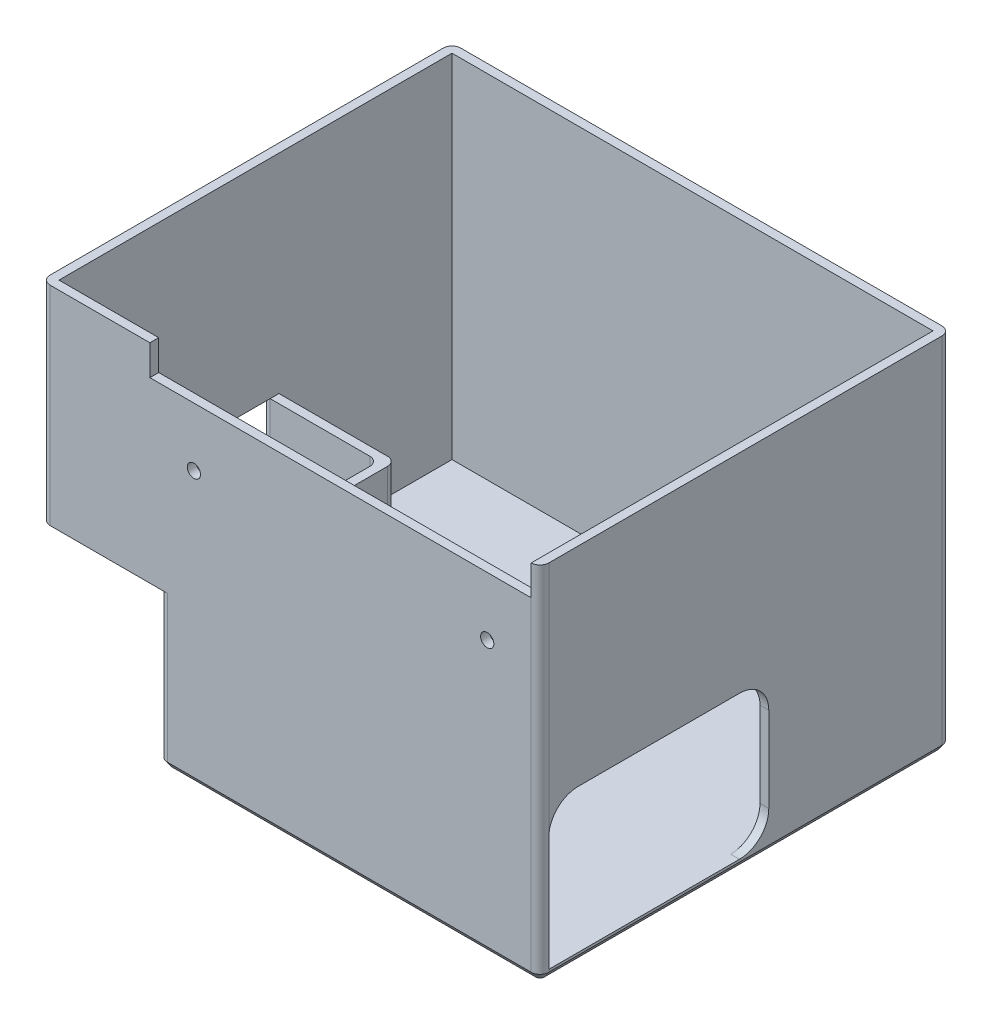
SolidWorks part; units mm, degrees
ref_plane "Front Plane" through (0, 0, 0) normal (0, 0, 1) x (1, 0, 0)
ref_plane "Top Plane" through (0, 0, 0) normal (0, 1, 0) x (1, 0, 0)
ref_plane "Right Plane" through (0, 0, 0) normal (1, 0, 0) x (0, 0, -1)
sketch "Sketch1" plane through (0, 0, 0) normal (0, 1, 0) x (1, 0, 0)
  line L1 (-85, -70) -> (85, -70)
  line L2 (-85, -70) -> (-85, 70)
  line L3 (-85, 70) -> (85, 70)
  line L4 (85, -70) -> (85, 70)
  line L5 (-85, -70) -> (85, 70) construction
  line L6 (-85, 70) -> (85, -70) construction
  point P0 (0, 0)
  dimension "D1" = 170
  dimension "D2" = 140
extrude "Boss-Extrude1" add sketch "Sketch1" along normal blind 3
sketch "Sketch3" plane through (0, 3, 0) normal (0, 1, 0) x (1, 0, 0)
  line L0 (82, -67) -> (82, 67)
  line L1 (82, 67) -> (-82, 67)
  line L2 (-82, 67) -> (-82, -67)
  line L3 (-82, -67) -> (82, -67)
  line L4 (85, -70) -> (85, 70)
  line L5 (85, 70) -> (-85, 70)
  line L6 (-85, 70) -> (-85, -70)
  line L7 (-85, -70) -> (85, -70)
  line L8 (85, -70) -> (85, 70)
  line L9 (85, 70) -> (-85, 70)
  line L10 (-85, 70) -> (-85, -70)
  line L11 (-85, -70) -> (85, -70)
  dimension "D1" = 0
  dimension "D2" = 3
extrude "Boss-Extrude2" add sketch "Sketch3" along normal blind 120
sketch "Sketch4" plane through (0, 0, 70) normal (0, 0, 1) x (1, 0, 0)
  line L0 (-85, 123) -> (85, 123) construction
  line L1 (82, 123) -> (-48, 123)
  line L2 (82, 123) -> (82, 112.7)
  line L3 (82, 112.7) -> (-48, 112.7)
  line L4 (-48, 123) -> (-48, 112.7)
  line L5 (82, 123) -> (82, 3) construction
  dimension "D1" = 10.3
  dimension "D2" = 130
extrude "Cut-Extrude1" cut sketch "Sketch4" against normal up to next
sketch "Sketch5" plane through (-85, 0, 0) normal (-1, 0, 0) x (0, 0, 1)
  line L0 (-70, 123) -> (70, 123) construction
  line L1 (-5, 0) -> (70, 0)
  line L2 (-5, 0) -> (-5, 52)
  line L3 (-5, 52) -> (70, 52)
  line L4 (70, 0) -> (70, 52)
  line L7 (-70, 0) -> (70, 0) construction
  line L8 (70, 123) -> (70, 0) construction
  dimension "D1" = 71
  dimension "D2" = 75
extrude "Cut-Extrude2" cut sketch "Sketch5" against normal blind 40
sketch "Sketch6" plane through (0, 3, 0) normal (0, 1, 0) x (1, 0, 0)
  line L0 (-45, 5) -> (-45, -67) construction
  line L1 (-82, 5) -> (-45, 5) construction
  line L2 (-45, 5) -> (-45, -67)
  line L3 (-82, 5) -> (-45, 5)
  line L4 (-82, 5) -> (-82, 8)
  line L5 (-82, 67) -> (-82, 5) construction
  line L6 (-82, 8) -> (-42, 8)
  line L7 (-42, 8) -> (-42, -67)
  line L8 (-48, -67) -> (82, -67) construction
  line L9 (-42, -67) -> (-45, -67)
  dimension "D1" = 3
extrude "Boss-Extrude3" add sketch "Sketch6" along normal up to surface (49 mm away) up to face at (-70.6667, 52, 44)
sketch "Sketch8" plane through (0, 0, 70) normal (0, 0, 1) x (1, 0, 0)
  line L0 (-48, 112.7) -> (82, 112.7) construction
  line L2 (82, 112.7) -> (82, 123) construction
  circle A0 centre (67, 92.7) radius 2.25
  circle A1 centre (-33, 92.7) radius 2.25
  dimension "D1" = 4.5
  dimension "D2" = 20
  dimension "D3" = 15
  dimension "D4" = 100
extrude "Cut-Extrude3" cut sketch "Sketch8" against normal up to next
sketch "Sketch9" plane through (85, 0, 0) normal (1, 0, 0) x (0, 0, -1)
  line L0 (-67, 3) -> (67, 3) construction
  line L2 (-67, 112.7) -> (-67, 3) construction
  line L3 (-67, 3) -> (8, 3) construction
  line L5 (-67, 112.7) -> (-67, 3) construction
  line L6 (-70, 123) -> (70, 123) construction
  line L7 (8, 3) -> (-67, 3)
  line L8 (8, 3) -> (8, 52)
  line L9 (8, 52) -> (-67, 52)
  line L10 (-67, 3) -> (-67, 52)
  point P8 (67, 3)
  dimension "D1" = 71
  dimension "D2" = 75
extrude "Cut-Extrude4" cut sketch "Sketch9" against normal up to next
fillet "Fillet1" radius 3 8 edges at (-45, 26, 70) (-85, 26, -5) (-42, 27.5, -8) (-45, 26, -5) (85, 61.5, -70) (85, 61.5, 70) (-85, 61.5, -70) (-85, 87.5, 70)
chamfer "Chamfer1" distance 1.5 angle 55 12 edges at (84.1213, 0, 69.1213) (85, 0, 0) (84.1213, 0, -69.1213) (0, 0, -70) (-84.1213, 0, -69.1213) (-85, 0, -37.5) (-84.1213, 0, -5.8787) (-65, 0, -5) (-45.8787, 0, -4.1213) (-45, 0, 32.5) (-44.1213, 0, 69.1213) (20, 0, 70) first distance on face at (-15, 0, -1.6667)
fillet "Fillet2" radius 10 3 edges at (83.5, 52, 67) (83.5, 52, -8) (83.5, 3, -8)
